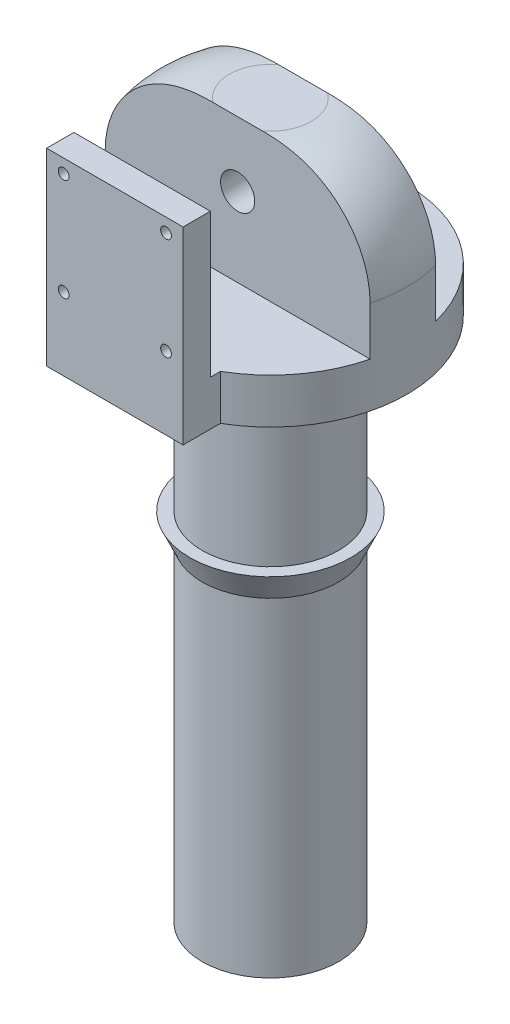
SolidWorks part; units mm, degrees
ref_plane "Front Plane" through (0, 0, 0) normal (0, 0, 1) x (1, 0, 0)
ref_plane "Top Plane" through (0, 0, 0) normal (0, 1, 0) x (1, 0, 0)
ref_plane "Right Plane" through (0, 0, 0) normal (1, 0, 0) x (0, 0, -1)
sketch "Sketch1" plane through (0, 0, 0) normal (0, 1, 0) x (1, 0, 0)
  circle A0 centre (0, 0) radius 12.7
  dimension "D1" = 25.4
extrude "Part that goes into base" add sketch "Sketch1" along normal blind 97.79
sketch "Sketch2" plane through (0, 0, 0) normal (0, 0, 1) x (1, 0, 0)
  line L0 (12.7, 97.79) -> (-12.7, 97.79) construction
  line L1 (12.7, 97.79) -> (-12.7, 97.79)
  line L2 (12.7, 97.79) -> (12.7, 66.294) construction
  line L3 (12.7, 66.294) -> (14.986, 66.294)
  line L4 (14.986, 66.294) -> (12.7, 61.214)
  line L5 (12.7, 61.214) -> (12.7, 66.294)
  line L6 (0, 97.79) -> (0, 52.1662) construction
  dimension "D1" = 31.496
  dimension "D2" = 2.286
  dimension "D3" = 5.08
revolve "Clip in mechanism" add sketch "Sketch2" angle 360 about L6 region at (13.462, 64.6007, 0)
sketch "Sketch3" plane through (0, 97.79, 0) normal (0, 1, 0) x (1, 0, 0)
  circle A0 centre (0, 0) radius 25.4
  dimension "D1" = 50.8
extrude "Top part Extrude" add sketch "Sketch3" along normal blind 35.14
ref_plane "Plane1" through (50.8, 0, 0) normal (1, 0, 0) x (0, 0, -1)
sketch "Sketch4" plane through (50.8, 0, 0) normal (1, 0, 0) x (0, 0, -1)
  line L0 (25.4, 132.93) -> (-25.4, 132.93) construction
  line L1 (25.4, 132.93) -> (-23.876, 132.93)
  line L2 (-12.7, 97.79) -> (12.7, 97.79) construction
  line L8 (6.096, 132.93) -> (6.096, 106.172)
  line L10 (25.4, 97.79) -> (25.4, 132.93) construction
  line L11 (25.4, 106.172) -> (25.4, 132.93)
  line L12 (6.096, 132.93) -> (25.4, 132.93)
  line L13 (25.4, 106.172) -> (6.096, 106.172)
  line L14 (-23.876, 106.172) -> (-6.096, 106.172)
  line L15 (-23.876, 132.93) -> (-6.096, 132.93)
  line L18 (-6.096, 132.93) -> (-6.096, 106.172)
  line L19 (-23.876, 132.93) -> (-23.876, 106.172)
  dimension "D1" = 8.382
  dimension "D3" = 8.382
  dimension "D4" = 19.304
  dimension "D5" = 8.382
  dimension "D6" = 19.304
  dimension "D7" = 1.524
extrude "Cut to Accommodate Encoder" cut sketch "Sketch4" against normal through all
sketch "Sketch5" plane through (0, 106.172, 0) normal (0, 1, 0) x (1, 0, 0)
  line L0 (-13.191, -27.686) -> (15.1785, -27.686)
  line L1 (24.6576, -6.096) -> (24.6576, -40.386)
  line L2 (-24.6576, -6.096) -> (24.6576, -6.096) construction
  line L3 (-24.6576, -6.096) -> (-24.6576, -40.386)
  line L4 (-24.6576, -40.386) -> (24.6576, -40.386)
  arc A0 (24.6576, -6.096) -> (-24.6576, -6.096) centre (0, 0) cw
  dimension "D1" = 21.59
  dimension "D2" = 34.29
sketch "Sketch7" plane through (0, 0, -6.096) normal (0, 0, -1) x (-1, 0, 0)
  line L0 (0, 132.93) -> (0, 120.865) construction
  line L1 (24.6576, 132.93) -> (-24.6576, 132.93) construction
  circle A0 centre (0, 120.865) radius 3.175
  dimension "D2" = 6.35
  dimension "D1" = 12.065
extrude "Bolt Hole" cut sketch "Sketch7" against normal up to surface (12.192 mm away) up to face at (0, 119.551, 6.096)
fillet "Fillet to Accommodate shoulder" radius 17.78 2 edges at (-25.4, 132.93, 0) (25.4, 132.93, 0)
ref_plane "Plane2" through (0, 0, 26.416) normal (0, 0, 1) x (1, 0, 0)
sketch "Sketch11" plane through (0, 132.93, 0) normal (0, 1, 0) x (1, 0, 0)
  line L1 (12.7, -23.876) -> (12.7, -28.956)
  line L2 (12.7, -28.956) -> (-12.7, -28.956)
  line L3 (-12.7, -28.956) -> (-12.7, -23.876)
  line L5 (0, 0) -> (0, -31.0003) construction
  line L8 (-8.6658, -23.876) -> (-12.7, -23.876)
  line L9 (8.6658, -23.876) -> (12.7, -23.876)
  line L10 (-8.6658, -23.876) -> (8.6658, -23.876) construction
  arc A0 (-8.6658, -23.876) -> (8.6658, -23.876) centre (0, 0) ccw
  dimension "D1" = 25.4
  dimension "D2" = 5.08
extrude "Boss-Extrude1" add sketch "Sketch11" against normal up to surface (35.14 mm away) up to face at (0, 97.79, 12.7)
sketch "Sketch12" plane through (0, 106.172, 0) normal (0, 1, 0) x (1, 0, 0)
  line L0 (12.7, -23.876) -> (12.7, -21.997)
  line L1 (-12.7, -23.876) -> (-12.7, -21.997)
  line L2 (-12.7, -23.876) -> (-8.6658, -23.876)
  line L3 (8.6658, -23.876) -> (12.7, -23.876)
  arc A0 (8.6658, -23.876) -> (24.6576, -6.096) centre (0, 0) ccw construction
  arc A1 (-24.6576, -6.096) -> (-8.6658, -23.876) centre (0, 0) ccw construction
  arc A2 (-8.6658, -23.876) -> (-12.7, -21.997) centre (0, 0) cw
  arc A3 (12.7, -21.997) -> (8.6658, -23.876) centre (0, 0) cw
extrude "Boss-Extrude2" add sketch "Sketch12" against normal up to surface (8.382 mm away) up to face at (0, 97.79, 12.7)
sketch "Sketch13" plane through (0, 0, 23.876) normal (0, 0, -1) x (-1, 0, 0)
  line L0 (12.7, 132.93) -> (-12.7, 132.93) construction
  line L1 (0, 132.93) -> (0, 111.6123) construction
  line L2 (-12.7, 120.865) -> (12.3879, 120.865) construction
  line L3 (-12.7, 106.172) -> (-12.7, 132.93) construction
  circle A0 centre (9.525, 130.39) radius 1
  circle A1 centre (-9.525, 130.39) radius 1
  circle A2 centre (-9.525, 111.34) radius 1
  circle A3 centre (9.525, 111.34) radius 1
  circle A4 centre (0, 120.865) radius 3.175 construction
  circle A5 centre (0, 120.865) radius 3.175
  point P20 (0, 0)
  point P21 (0, 0)
  point P22 (0, 0)
  point P23 (0, 0)
  dimension "D1" = 9.525
  dimension "D2" = 9.525
  dimension "D3" = 2.54
  dimension "D4" = 0
extrude "Cut-Extrude1" cut sketch "Sketch13" against normal up to surface (5.08 mm away) contours A2 | A1 | A3 | A0 region at (9.525, 111.34, 23.876) up to face at (0, 115.36, 28.956)
